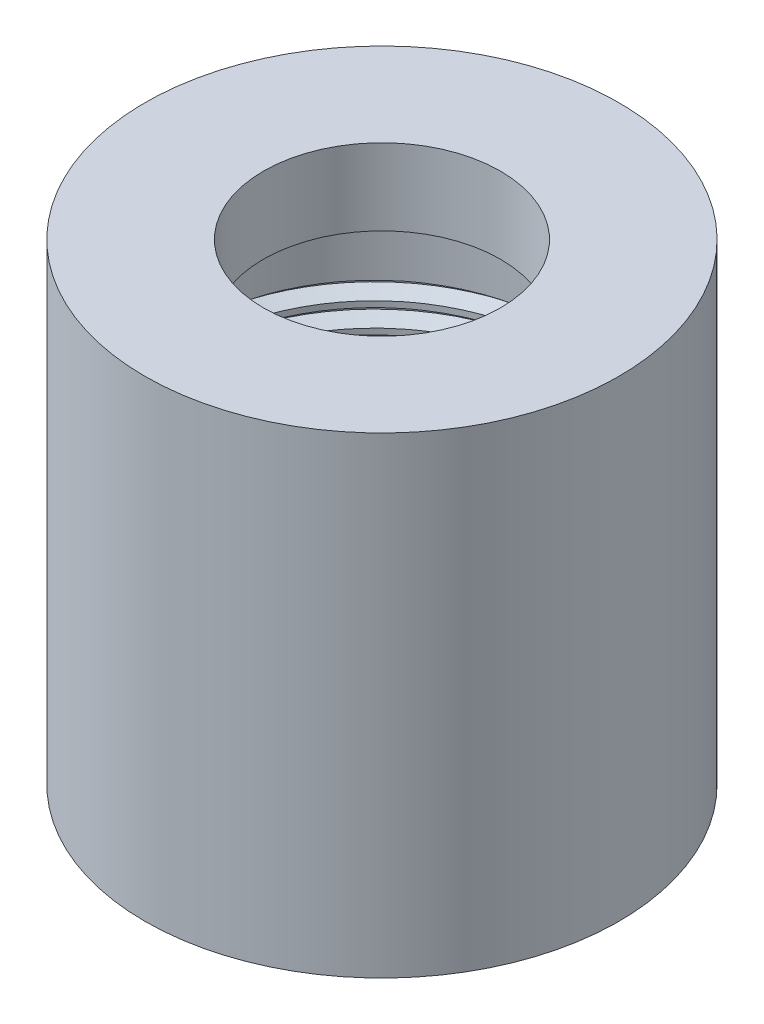
SolidWorks part; units mm, degrees
ref_plane "Front Plane" through (0, 0, 0) normal (0, 0, 1) x (1, 0, 0)
ref_plane "Top Plane" through (0, 0, 0) normal (0, 1, 0) x (1, 0, 0)
ref_plane "Right Plane" through (0, 0, 0) normal (1, 0, 0) x (0, 0, -1)
sketch "Sketch1" plane through (0, 0, 0) normal (1, 0, 0) x (0, 0, -1)
  line L0 (0, 108.3463) -> (0, -41.6537) construction
  line L1 (-36.5359, 143.3113) -> (174.1308, 143.3113) construction
  line L2 (-7.5, -41.6537) -> (7.5, -41.6537) construction
  line L3 (10, 87.0265) -> (20, 87.0265)
  line L4 (20, 87.0265) -> (20, 47.1887)
  line L5 (20, 47.1887) -> (15, 47.1887)
  line L6 (15, 47.1887) -> (15, 80.5878)
  line L7 (15, 80.5878) -> (10, 80.5878)
  line L8 (10, 80.5878) -> (10, 87.0265)
  line L12 (0, 112.6014) -> (0, 3.4775) construction
  point P8 (0, -41.6537)
  dimension "D1" = 150
  dimension "D2" = 15
  dimension "D3" = 15
  dimension "D4" = 10
revolve "Revolve2" add sketch "Sketch1" angle 360 about L0
thread "Thread1" pitch 2 method cut profile "Thread Profile1" start angle 0, offset 0, length 25, pitch 2, diameter 30
ref_plane "Plane4" through (15, 47.1887, 0) normal (0, 0, 1) x (1, 0, 0)
sketch "Thread Profile1" plane through (15, 47.1887, 0) normal (0, 0, 1) x (1, 0, 0)
  line L0 (0, 0) -> (0, 2) construction
  line L1 (0, 0) -> (1.0825, 0.625)
  line L2 (1.0825, 0.625) -> (1.0825, 0.875)
  line L3 (1.0825, 0.875) -> (0, 1.5)
  line L4 (1.0825, 0.75) -> (0, 0.75) construction
  line L11 (0, 0) -> (0, 1.5)
  point P2 (0, 0)
  dimension "Pitch" = 2
  dimension "Profile_Angle" = 60
  dimension "Profile_Land" = 0.25
  dimension "Profile_Height" = 1.0825
